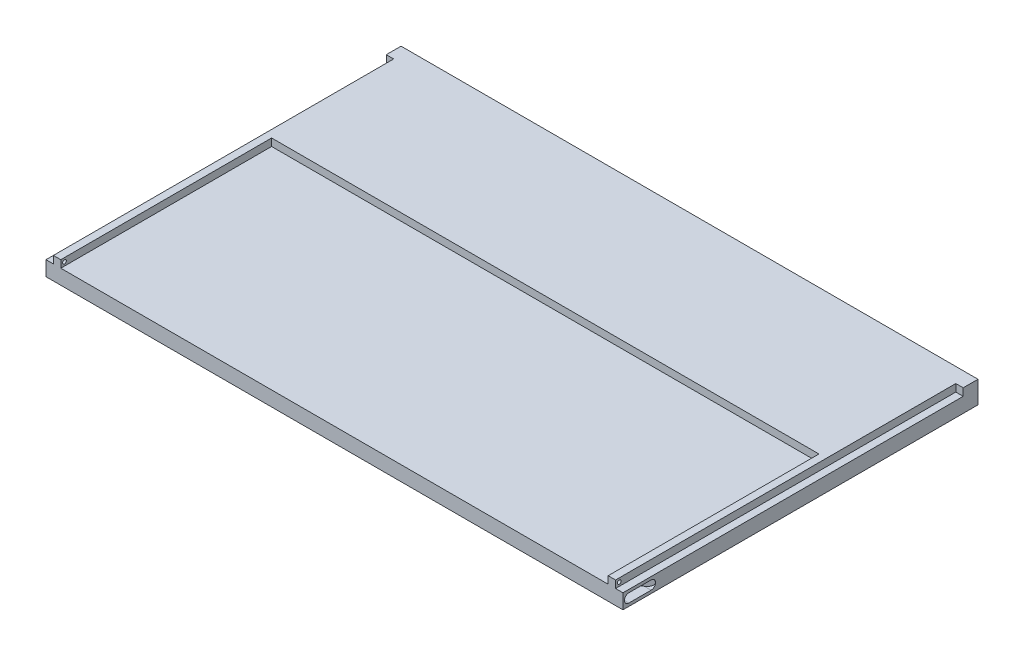
SolidWorks part; units mm, degrees
other "Markup1"
sketch "Sketch12" plane through (250.825, 22.225, 158.75) normal (0.1153, 0.0728, 0.9907) x (0.9687, -0.2289, -0.0959)
material "6061 Alloy"
ref_plane "Front Plane" through (0, 0, 0) normal (0, 0, 1) x (1, 0, 0)
ref_plane "Top Plane" through (0, 0, 0) normal (0, 1, 0) x (1, 0, 0)
ref_plane "Right Plane" through (0, 0, 0) normal (1, 0, 0) x (0, 0, -1)
sketch "Sketch1" plane through (0, 0, 0) normal (0, 1, 0) x (1, 0, 0)
  line L1 (-241.3, 152.4) -> (241.3, 152.4)
  line L2 (-241.3, 152.4) -> (-241.3, -152.4)
  line L3 (-241.3, -152.4) -> (241.3, -152.4)
  line L4 (241.3, 152.4) -> (241.3, -152.4)
  line L5 (-241.3, 152.4) -> (241.3, -152.4) construction
  line L6 (-241.3, -152.4) -> (241.3, 152.4) construction
  point P0 (0, 0)
  dimension "D1" = 482.6
  dimension "D2" = 304.8
extrude "Boss-Extrude1" add sketch "Sketch1" along normal blind 12.7
sketch "Sketch2" plane through (0, 12.7, 0) normal (0, 1, 0) x (1, 0, 0)
  line L0 (-241.3, -152.4) -> (241.3, -152.4) construction
  line L1 (-241.3, 152.4) -> (-234.95, 152.4)
  line L2 (-241.3, 152.4) -> (-241.3, -152.4)
  line L3 (-241.3, -152.4) -> (-234.95, -152.4)
  line L4 (-234.95, 28.575) -> (-234.95, -152.4)
  line L5 (241.3, 152.4) -> (-241.3, 152.4) construction
  line L6 (241.3, 152.4) -> (234.95, 152.4)
  line L7 (241.3, 152.4) -> (241.3, -152.4)
  line L8 (241.3, -152.4) -> (234.95, -152.4)
  line L9 (234.95, 28.575) -> (234.95, -152.4)
  line L10 (-234.95, 152.4) -> (234.95, 152.4)
  line L12 (-234.95, 28.575) -> (234.95, 28.575)
  point P14 (-238.125, -152.4)
  dimension "D1" = 6.35
  dimension "D2" = 180.975
extrude "Boss-Extrude2" add sketch "Sketch2" along normal blind 6.35
sketch "Sketch3" plane through (-241.3, 0, 0) normal (-1, 0, 0) x (0, 0, 1)
  line L0 (152.4, 19.05) -> (152.4, 0) construction
  line L1 (-152.4, 19.05) -> (152.4, 19.05) construction
  circle A0 centre (149.225, 15.875) radius 1.5875
  dimension "D3" = 3.175
  dimension "D1" = 3.175
  dimension "D2" = 3.175
extrude "Cut-Extrude1" cut sketch "Sketch3" against normal through all
sketch "Sketch4" plane through (0, 0, 152.4) normal (0, 0, 1) x (1, 0, 0)
  line L0 (-241.3, 19.05) -> (-241.3, 0) construction
  line L1 (-241.3, 12.7) -> (-247.65, 12.7)
  line L2 (-241.3, 12.7) -> (-241.3, 0)
  line L3 (-241.3, 0) -> (-247.65, 0)
  line L4 (-247.65, 12.7) -> (-247.65, 0)
  line L5 (-241.3, 0) -> (241.3, 0) construction
  dimension "D1" = 12.7
  dimension "D2" = 6.35
extrude "Boss-Extrude3" add sketch "Sketch4" against normal blind 292.1
sketch "Sketch5" plane through (-241.3, 0, 0) normal (-1, 0, 0) x (0, 0, 1)
  line L0 (-152.4, 0) -> (-139.7, 0) construction
  line L1 (-152.4, 19.05) -> (-139.7, 19.05)
  line L2 (-152.4, 19.05) -> (-152.4, 0)
  line L3 (-152.4, 0) -> (-139.7, 0)
  line L4 (-139.7, 19.05) -> (-139.7, 0)
  line L5 (-139.7, 0) -> (-139.7, 12.7) construction
extrude "Boss-Extrude4" add sketch "Sketch5" along normal up to surface (6.35 mm away) up to face at (-247.65, 6.35, 6.35)
mirror "Mirror1" about plane through (0, 0, 0) normal (1, 0, 0) of "Boss-Extrude4", "Boss-Extrude3"
sketch "Sketch6" plane through (-241.3, 0, 0) normal (-1, 0, 0) x (0, 0, 1)
  line L0 (147.32, 6.35) -> (128.27, 6.35) construction
  line L1 (147.32, 2.54) -> (128.27, 2.54)
  line L2 (147.32, 10.16) -> (128.27, 10.16)
  line L3 (152.4, 19.05) -> (152.4, 12.7) construction
  line L5 (152.4, 12.7) -> (152.4, 0) construction
  arc A0 (147.32, 2.54) -> (147.32, 10.16) centre (147.32, 6.35) ccw
  arc A1 (128.27, 10.16) -> (128.27, 2.54) centre (128.27, 6.35) ccw
  point P2 (137.795, 6.35)
  point P11 (152.4, 6.35)
  dimension "D1" = 19.05
  dimension "D2" = 5.08
  dimension "D3" = 7.62
extrude "Cut-Extrude2" cut sketch "Sketch6" against normal blind 25.4 from surface starting at face at (-247.65, 10.5833, -46.5667)
extrude "Cut-Extrude3" cut sketch "Sketch6<2>" along normal blind 25.4 from surface starting at face at (247.65, 10.5833, -46.5667)
sketch "Sketch6<2>" plane through (-241.3, 0, 0) normal (-1, 0, 0) x (0, 0, 1) same geometry as "Sketch6"
sketch "Sketch11" plane through (0, 0, 0) normal (0, -1, 0) x (1, 0, 0)
  line L0 (-247.65, 124.46) -> (-222.25, 124.46)
  line L1 (-222.25, 124.46) -> (-222.25, 140.97)
  line L2 (-222.25, 140.97) -> (-247.65, 124.46)
  line L3 (-222.25, 128.27) -> (-222.25, 147.32) construction
  dimension "D1" = 10.16
extrude "Boss-Extrude5" add sketch "Sketch11" against normal up to surface (10.16 mm away) from surface up to face at (-234.95, 10.16, 137.795) starting at face at (-234.95, 2.54, 137.795)
mirror "Mirror2" about plane through (0, 0, 0) normal (1, 0, 0) of "Boss-Extrude5"
